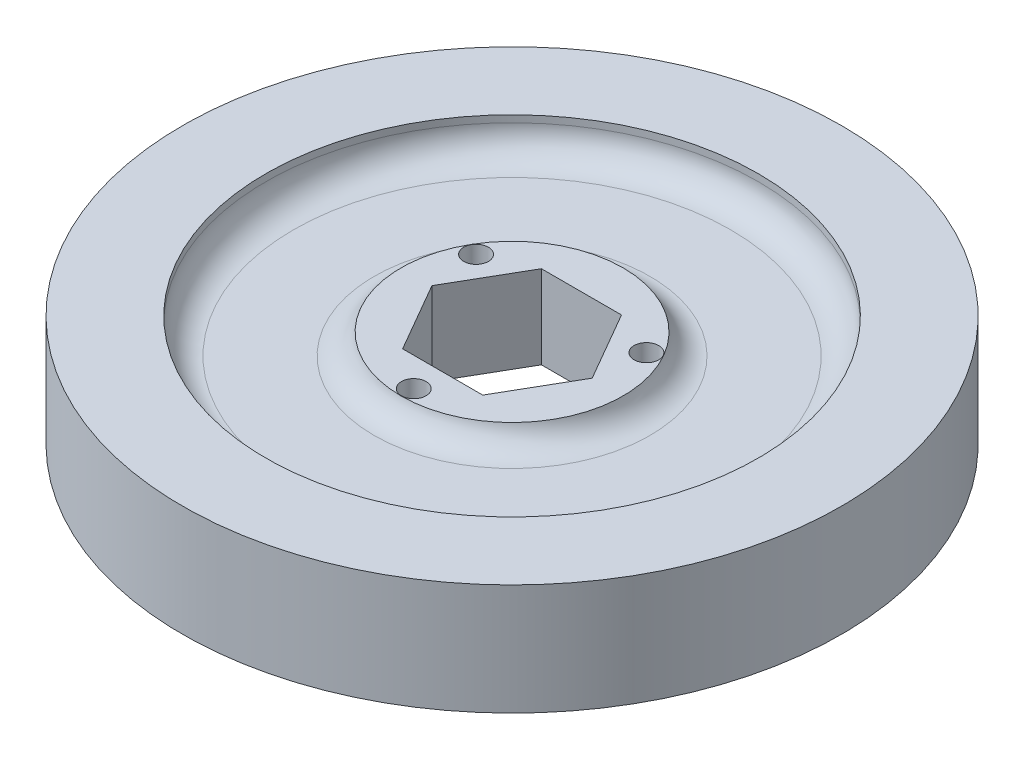
SolidWorks part; units mm, degrees
material "Rubber"
ref_plane "Front Plane" through (0, 0, 0) normal (0, 0, 1) x (1, 0, 0)
ref_plane "Top Plane" through (0, 0, 0) normal (0, 1, 0) x (1, 0, 0)
ref_plane "Right Plane" through (0, 0, 0) normal (1, 0, 0) x (0, 0, -1)
sketch "Sketch1" plane through (0, 0, 0) normal (0, 0, 1) x (1, 0, 0)
  line L0 (0, 0) -> (0, 9.2164) construction
  line L1 (10.16, -1.905) -> (10.16, -3.81)
  line L2 (0, 3.81) -> (10.16, 3.81)
  line L3 (0, 3.81) -> (0, -3.81)
  line L4 (0, -3.81) -> (10.16, -3.81)
  line L5 (10.16, 3.81) -> (10.16, 1.905)
  line L6 (10.16, 1.905) -> (22.5425, 1.905)
  line L7 (22.5425, -1.905) -> (22.5425, -5.08)
  line L8 (10.16, -1.905) -> (22.5425, -1.905)
  line L10 (22.5425, 5.08) -> (30.1625, 5.08)
  line L11 (22.5425, 5.08) -> (22.5425, 1.905)
  line L12 (22.5425, -5.08) -> (30.1625, -5.08)
  line L13 (30.1625, 5.08) -> (30.1625, -5.08)
  dimension "D1" = 7.62
  dimension "D2" = 10.16
  dimension "D3" = 3.81
  dimension "D4" = 22.5425
  dimension "D5" = 30.1625
  dimension "D6" = 10.16
revolve "Revolve1" add sketch "Sketch1" angle 360 about L0
fillet "Fillet1" radius 2.54 2 edges at (0, 1.905, -22.5425) (0, 1.905, -10.16)
fillet "Fillet2" radius 2.54 2 edges at (0, -1.905, -10.16) (0, -1.905, -22.5425)
sketch "Sketch2" plane through (0, -3.81, 0) normal (0, -1, 0) x (1, 0, 0)
  line L1 (3.6662, 6.35) -> (-3.6662, 6.35)
  line L2 (-3.6662, 6.35) -> (-7.3323, 0)
  line L3 (-7.3323, 0) -> (-3.6662, -6.35)
  line L4 (-3.6662, -6.35) -> (3.6662, -6.35)
  line L5 (3.6662, -6.35) -> (7.3323, 0)
  line L6 (7.3323, 0) -> (3.6662, 6.35)
  circle A0 centre (0, 0) radius 6.35 construction
  dimension "D1" = 12.7
extrude "Cut-Extrude1" cut sketch "Sketch2" against normal through all
hole_wizard "#4-40 Tapped Hole1" positions "Sketch3" profile "Sketch4" tap size "#4-40" standard "ANSI Inch" end condition through all
sketch "Sketch3" plane through (0, 3.81, 0) normal (0, 1, 0) x (1, 0, 0)
  point P0 (0, -9)
  point P3 (-7.7942, 4.5)
  point P6 (7.7942, 4.5)
sketch "Sketch4" plane through (0, 3.81, 9) normal (1, 0, 0) x (0, 0, 1)
  line L0 (0, 0) -> (0, 8.89)
  line L1 (0, 8.89) -> (1.1303, 8.89)
  line L2 (1.1303, 8.89) -> (1.1303, 0)
  line L5 (1.1303, 0) -> (0, 0)
  line L11 (0, -6.35) -> (0, 107.95) construction
  dimension "Thru Tap Drill Dia." = 2.2606
  dimension "Thru Tap Drill Depth" = 8.89
cosmetic thread "Hole Thread1" parameters "D2"=2.8448
cosmetic thread "Hole Thread2" parameters "D2"=2.8448
cosmetic thread "Hole Thread3" parameters "D2"=2.8448
